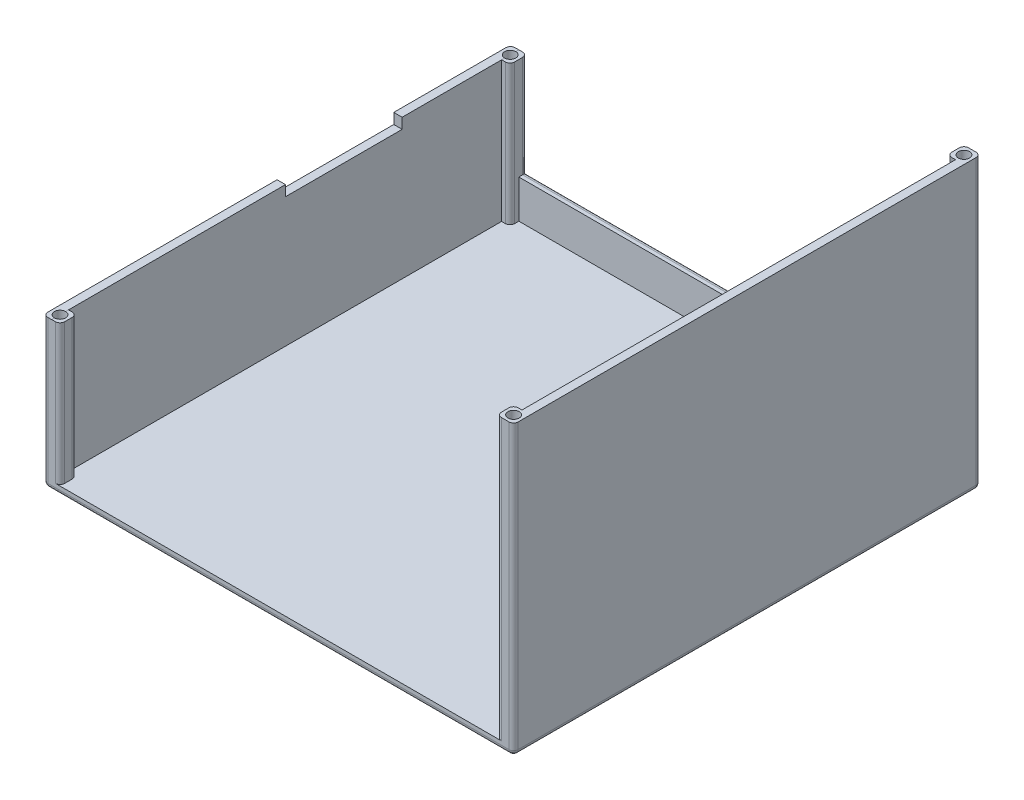
SolidWorks part; units mm, degrees
ref_plane "Front Plane" through (0, 0, 0) normal (0, 0, 1) x (1, 0, 0)
ref_plane "Top Plane" through (0, 0, 0) normal (0, 1, 0) x (1, 0, 0)
ref_plane "Right Plane" through (0, 0, 0) normal (1, 0, 0) x (0, 0, -1)
other "Bounding Box"
ref_plane "Default Plane" through (0, 78.486, -127.1251) normal (0, 0, 1) x (1, 0, 0)
sketch "Sketch1" plane through (0, 0, 0) normal (0, 1, 0) x (1, 0, 0)
  line L1 (0, 0) -> (127.979, 0)
  line L2 (0, 0) -> (0, 127.1251)
  line L3 (0, 127.1251) -> (127.979, 127.1251)
  line L4 (127.979, 0) -> (127.979, 127.1251)
extrude "Boss-Extrude1" add sketch "Sketch1" along normal blind 2.286 contours L3 L4 L1 L2
sketch "Sketch2" plane through (0, 2.286, 0) normal (0, 1, 0) x (1, 0, 0)
  line L1 (0, 127.1251) -> (127.979, 127.1251)
  line L2 (0, 127.1251) -> (0, 0)
  line L3 (0, 0) -> (127.979, 0)
  line L4 (127.979, 127.1251) -> (127.979, 0)
  dimension "D1" = 127.1251
  dimension "D2" = 127.979
extrude "Boss-Extrude2" add sketch "Sketch2" along normal blind 76.2
sketch "Sketch4" plane through (0, 78.486, 0) normal (0, 1, 0) x (1, 0, 0)
  line L0 (0, 127.1251) -> (0, 0) construction
  line L1 (2.286, 124.8391) -> (125.693, 124.8391)
  line L2 (2.286, 124.8391) -> (2.286, 2.286)
  line L3 (2.286, 2.286) -> (125.693, 2.286)
  line L4 (125.693, 124.8391) -> (125.693, 2.286)
  line L5 (127.979, 127.1251) -> (0, 127.1251) construction
  line L6 (127.979, 0) -> (127.979, 127.1251) construction
  line L7 (0, 0) -> (127.979, 0) construction
  dimension "D1" = 2.286
  dimension "D2" = 2.286
  dimension "D3" = 2.286
  dimension "D4" = 2.286
extrude "Cut-Extrude2" cut sketch "Sketch4" against normal blind 76.2 contours L1 L4 L3 L2
sketch "Sketch5" plane through (0, 0, 0) normal (0, 0, 1) x (1, 0, 0)
  line L0 (0, 78.486) -> (0, 0) construction
  line L1 (2.286, 78.486) -> (125.693, 78.486)
  line L2 (2.286, 78.486) -> (2.286, 2.286)
  line L3 (2.286, 2.286) -> (125.693, 2.286)
  line L4 (125.693, 78.486) -> (125.693, 2.286)
  line L5 (127.979, 78.486) -> (127.979, 0) construction
  line L6 (0, 0) -> (127.979, 0) construction
  dimension "D1" = 2.286
  dimension "D2" = 2.286
  dimension "D3" = 2.286
extrude "Cut-Extrude3" cut sketch "Sketch5" against normal blind 2.286
sketch "Sketch6" plane through (0, 0, -127.1251) normal (0, 0, -1) x (-1, 0, 0)
  line L0 (-127.979, 78.486) -> (-127.979, 0) construction
  line L1 (-125.693, 78.486) -> (-2.286, 78.486)
  line L2 (-125.693, 78.486) -> (-125.693, 12.7)
  line L3 (-125.693, 12.7) -> (-2.286, 12.7)
  line L4 (-2.286, 78.486) -> (-2.286, 12.7)
  line L5 (0, 78.486) -> (0, 0) construction
  line L6 (0, 0) -> (-127.979, 0) construction
  dimension "D1" = 2.286
  dimension "D2" = 2.286
  dimension "D3" = 12.7
extrude "Cut-Extrude4" cut sketch "Sketch6" against normal blind 2.286
sketch "Sketch7" plane through (0, 0, 0) normal (-1, 0, 0) x (0, 0, 1)
  line L0 (0, 78.486) -> (0, 0) construction
  line L1 (-127.1251, 78.486) -> (0, 78.486)
  line L2 (-127.1251, 78.486) -> (-127.1251, 40.373)
  line L3 (-127.1251, 40.373) -> (0, 40.373)
  line L4 (0, 78.486) -> (0, 40.373)
extrude "Cut-Extrude5" cut sketch "Sketch7" against normal blind 2.286
sketch "Sketch8" plane through (0, 0, 0) normal (-1, 0, 0) x (0, 0, 1)
  line L0 (-127.1251, 40.373) -> (0, 40.373) construction
  line L1 (-95.3751, 40.373) -> (-63.6251, 40.373)
  line L2 (-95.3751, 40.373) -> (-95.3751, 37.5182)
  line L3 (-95.3751, 37.5182) -> (-63.6251, 37.5182)
  line L4 (-63.6251, 40.373) -> (-63.6251, 37.5182)
  line L5 (-127.1251, 40.373) -> (-127.1251, 0) construction
  point P8 (-63.6251, 38.9456)
  dimension "D1" = 31.75
  dimension "D2" = 31.75
extrude "Cut-Extrude6" cut sketch "Sketch8" against normal blind 2.54
sketch "Sketch9" plane through (0, 2.286, 0) normal (0, 1, 0) x (1, 0, 0)
  line L0 (127.979, 0) -> (127.979, 127.1251) construction
  line L1 (125.693, 0) -> (123.407, 0)
  line L2 (125.693, 0) -> (125.693, 4.572)
  line L3 (125.693, 4.572) -> (123.407, 4.572)
  line L4 (123.407, 0) -> (123.407, 4.572)
  dimension "D1" = 4.572
  dimension "D2" = 4.572
extrude "Boss-Extrude3" add sketch "Sketch9" along normal blind 76.2
sketch "Sketch11" plane through (0, 2.286, 0) normal (0, 1, 0) x (1, 0, 0)
  line L1 (2.286, 0) -> (4.572, 0)
  line L2 (2.286, 0) -> (2.286, 4.572)
  line L3 (2.286, 4.572) -> (4.572, 4.572)
  line L4 (4.572, 0) -> (4.572, 4.572)
extrude "Boss-Extrude5" add sketch "Sketch11" along normal blind 38.1
sketch "Sketch12" plane through (0, 12.7, 0) normal (0, 1, 0) x (1, 0, 0)
  line L1 (2.286, 127.1251) -> (4.572, 127.1251)
  line L2 (2.286, 127.1251) -> (2.286, 122.428)
  line L3 (2.286, 122.428) -> (4.572, 122.428)
  line L4 (4.572, 127.1251) -> (4.572, 122.428)
extrude "Boss-Extrude6" add sketch "Sketch12" along normal blind 27.686 and the other way blind 10.414
sketch "Sketch13" plane through (0, 12.7, 0) normal (0, 1, 0) x (1, 0, 0)
  line L0 (127.979, 0) -> (127.979, 127.1251) construction
  line L1 (125.693, 127.1251) -> (123.407, 127.1251)
  line L2 (125.693, 127.1251) -> (125.693, 122.5531)
  line L3 (125.693, 122.5531) -> (123.407, 122.5531)
  line L4 (123.407, 127.1251) -> (123.407, 122.5531)
  dimension "D1" = 4.572
  dimension "D2" = 4.572
extrude "Boss-Extrude7" add sketch "Sketch13" along normal blind 65.786 and the other way blind 10.414
sketch "Sketch14" plane through (0, 78.486, 0) normal (0, 1, 0) x (1, 0, 0)
  line L0 (127.979, 0) -> (127.979, 127.1251) construction
  line L3 (125.693, 4.572) -> (123.407, 4.572) construction
  line L4 (123.407, 0) -> (127.979, 0) construction
  circle A0 centre (125.693, 2.286) radius 1.524
  dimension "D1" = 2.286
  dimension "D2" = 2.286
  dimension "D3" = 2.286
extrude "Cut-Extrude7" cut sketch "Sketch14" against normal blind 6.35
sketch "Sketch15" plane through (0, 78.486, 0) normal (0, 1, 0) x (1, 0, 0)
  line L0 (123.407, 127.1251) -> (123.407, 122.5531) construction
  line L1 (127.979, 0) -> (127.979, 127.1251) construction
  line L2 (127.979, 127.1251) -> (123.407, 127.1251) construction
  line L3 (123.407, 122.5531) -> (125.693, 122.5531) construction
  circle A0 centre (125.693, 124.8391) radius 1.524
  dimension "D1" = 2.286
  dimension "D2" = 2.286
  dimension "D3" = 2.286
  dimension "D4" = 2.286
extrude "Cut-Extrude8" cut sketch "Sketch15" against normal blind 6.35
sketch "Sketch16" plane through (0, 40.373, 0) normal (0, 1, 0) x (1, 0, 0)
  line L0 (2.286, 4.572) -> (2.286, 0) construction
  line L1 (0, 63.6251) -> (0, 0) construction
  line L2 (4.572, 0) -> (4.572, 4.572) construction
  line L4 (2.286, 0) -> (0, 0) construction
  line L5 (4.572, 4.572) -> (2.286, 4.572) construction
  circle A0 centre (2.286, 2.286) radius 1.524
  dimension "D1" = 2.286
  dimension "D2" = 2.286
  dimension "D3" = 2.286
  dimension "D4" = 2.286
extrude "Cut-Extrude9" cut sketch "Sketch16" against normal blind 6.35
sketch "Sketch18" plane through (0, 40.386, 0) normal (0, 1, 0) x (1, 0, 0)
  line L0 (2.286, 4.572) -> (2.286, 0) construction
  circle A0 centre (2.286, 2.286) radius 1.524
extrude "Cut-Extrude10" cut sketch "Sketch18" against normal blind 6.35
sketch "Sketch19" plane through (0, 40.386, 0) normal (0, 1, 0) x (1, 0, 0)
  line L0 (2.286, 127.1251) -> (2.286, 122.428) construction
  circle A0 centre (2.286, 124.7766) radius 1.524
extrude "Cut-Extrude11" cut sketch "Sketch19" against normal blind 6.35
fillet "Fillet1" radius 1.27 1 edges at (0, 20.1865, 0)
fillet "Fillet2" radius 1.27 12 edges at (0.372, 0, -0.372) (123.407, 45.593, -127.1251) (127.979, 39.243, -127.1251) (127.979, 0, -63.5626) (63.9895, 0, -127.1251) (63.9895, 12.7, -127.1251) (4.572, 26.543, -127.1251) (0, 20.1865, -127.1251) (4.572, 21.336, -4.572) (4.572, 21.336, 0) (0, 0, -64.1976) (64.6245, 0, 0)
fillet "Fillet7" radius 1.27 1 edges at (4.572, 21.336, -122.428)
fillet "Fillet8" radius 1.27 5 edges at (127.607, 0.372, -0.372) (123.407, 40.386, -122.5531) (123.407, 40.386, -4.572) (127.979, 39.878, 0) (123.407, 40.386, 0)
